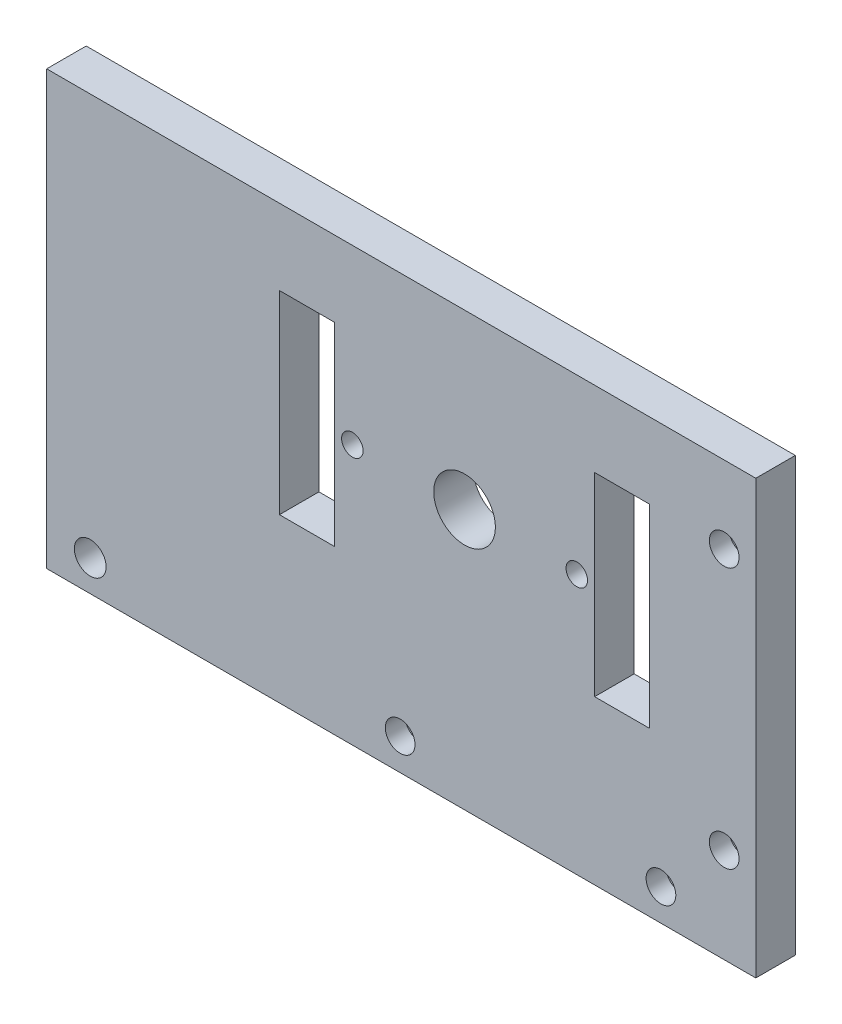
SolidWorks part; units mm, degrees
ref_plane "Front Plane" through (0, 0, 0) normal (0, 0, 1) x (1, 0, 0)
ref_plane "Top Plane" through (0, 0, 0) normal (0, 1, 0) x (1, 0, 0)
ref_plane "Right Plane" through (0, 0, 0) normal (1, 0, 0) x (0, 0, -1)
sketch "Brace Ref" plane through (0, 0, 0) normal (0, 0, 1) x (1, 0, 0)
  point P0 (0, 0)
  line B0 (-76.454, 5.6642) -> (-76.454, 10.0838)
  line B1 (-75.8588, 11.5206) -> (-73.7506, 13.6288)
  line B2 (-72.3138, 14.224) -> (-61.0148, 14.224)
  line B3 (-61.0148, 14.224) -> (-38.7641, 15.001)
  line B4 (-75.8588, 4.2274) -> (-73.7506, 2.1192)
  line B5 (-72.3138, 1.524) -> (-61.5696, 1.524)
  line B6 (-57.8366, 0) -> (-21.4114, 0)
  line B7 (-17.6784, 1.524) -> (-5.6642, 1.524)
  line B8 (-4.2274, 2.1192) -> (-2.1192, 4.2274)
  line B9 (-1.524, 5.6642) -> (-1.524, 17.6784)
  line B10 (0, 21.4114) -> (0, 57.8366)
  line B11 (-1.524, 61.5696) -> (-1.524, 72.3138)
  line B12 (-2.1192, 73.7506) -> (-4.2274, 75.8588)
  line B13 (-5.6642, 76.454) -> (-10.0838, 76.454)
  line B14 (-11.5206, 75.8588) -> (-13.6288, 73.7506)
  line B15 (-14.224, 72.3138) -> (-14.224, 61.0148)
  line B16 (-14.224, 61.0148) -> (-15.001, 38.7641)
  line B17 (-76.454, 0) -> (-76.454, 76.454) construction
  line B18 (-76.454, 0) -> (0, 0) construction
  line B19 (0, 0) -> (0, 76.454) construction
  line B20 (-76.454, 76.454) -> (0, 76.454) construction
  arc B21 (-76.454, 10.0838) -> (-75.8588, 11.5206) centre (-74.422, 10.0838) cw
  arc B22 (-73.7506, 13.6288) -> (-72.3138, 14.224) centre (-72.3138, 12.192) cw
  arc B23 (-38.7641, 15.001) -> (-27.0035, 18.4638) centre (-39.624, 39.624) ccw
  arc B24 (-27.0035, 18.4638) -> (-25.4333, 20.7849) centre (-28.6949, 21.2997) ccw
  arc B25 (-25.4333, 20.7849) -> (-20.7849, 25.4333) centre (-19.9136, 19.9136) cw
  arc B26 (-76.454, 5.6642) -> (-75.8588, 4.2274) centre (-74.422, 5.6642) ccw
  arc B27 (-73.7506, 2.1192) -> (-72.3138, 1.524) centre (-72.3138, 3.556) ccw
  arc B28 (-61.5696, 1.524) -> (-59.2587, 0.5806) centre (-61.5696, -1.778) cw
  arc B29 (-59.2587, 0.5806) -> (-57.8366, 0) centre (-57.8366, 2.032) ccw
  arc B30 (-21.4114, 0) -> (-19.9893, 0.5806) centre (-21.4114, 2.032) ccw
  arc B31 (-19.9893, 0.5806) -> (-17.6784, 1.524) centre (-17.6784, -1.778) cw
  arc B32 (-5.6642, 1.524) -> (-4.2274, 2.1192) centre (-5.6642, 3.556) ccw
  arc B33 (-2.1192, 4.2274) -> (-1.524, 5.6642) centre (-3.556, 5.6642) ccw
  arc B34 (-1.524, 17.6784) -> (-0.5806, 19.9893) centre (1.778, 17.6784) cw
  arc B35 (-0.5806, 19.9893) -> (0, 21.4114) centre (-2.032, 21.4114) ccw
  arc B36 (0, 57.8366) -> (-0.5806, 59.2587) centre (-2.032, 57.8366) ccw
  arc B37 (-0.5806, 59.2587) -> (-1.524, 61.5696) centre (1.778, 61.5696) cw
  arc B38 (-1.524, 72.3138) -> (-2.1192, 73.7506) centre (-3.556, 72.3138) ccw
  arc B39 (-4.2274, 75.8588) -> (-5.6642, 76.454) centre (-5.6642, 74.422) ccw
  arc B40 (-10.0838, 76.454) -> (-11.5206, 75.8588) centre (-10.0838, 74.422) ccw
  arc B41 (-13.6288, 73.7506) -> (-14.224, 72.3138) centre (-12.192, 72.3138) ccw
  arc B42 (-15.001, 38.7641) -> (-18.4638, 27.0035) centre (-39.624, 39.624) cw
  arc B43 (-18.4638, 27.0035) -> (-20.7849, 25.4333) centre (-21.2997, 28.6949) cw
  circle B44 centre (-70.104, 7.874) radius 4.3561
  circle B45 centre (-19.9136, 19.9136) radius 2.3813
  circle B46 centre (-7.874, 70.104) radius 4.3561
sketch_block_instance "Block1-1"
sketch_block "Block1" parameters "D1"=31.75, "D2"=30.48, "D3"=30.48, "D4"=31.75, "D5"=19.7104, "D6"=19.7104
sketch "Sketch5" plane through (0, 0, 0) normal (0, 0, 1) x (1, 0, 0)
  line L0 (-49.594, 49.547) -> (-49.594, 44.594) construction
  line L1 (-91.344, 72.344) -> (-2.794, 72.344)
  line L2 (-91.344, 72.344) -> (-91.344, 2.794)
  line L3 (-91.344, 2.794) -> (-2.794, 2.794)
  line L4 (-2.794, 72.344) -> (-2.794, 2.794)
  line L6 (-79.594, 60.594) -> (-19.594, 60.594) construction
  line L7 (-79.594, 60.594) -> (-79.594, 28.594) construction
  line L8 (-67.628, 44.594) -> (-49.594, 44.594) construction
  line L9 (-81.344, 62.344) -> (-17.844, 62.344) construction
  line L10 (-49.594, 44.594) -> (-31.56, 44.594) construction
  line L11 (-81.344, 62.344) -> (-81.344, 26.844) construction
  line L12 (-81.344, 26.844) -> (-17.844, 26.844) construction
  line L13 (-17.844, 62.344) -> (-17.844, 26.844) construction
  line L14 (-86.344, 67.344) -> (-12.844, 67.344) construction
  line L15 (-79.594, 28.594) -> (-19.594, 28.594) construction
  line L16 (-19.594, 60.594) -> (-19.594, 28.594) construction
  line L17 (-79.344, 60.194) -> (-70.494, 60.194)
  line L18 (-86.344, 67.344) -> (-86.344, 21.844) construction
  line L19 (-86.344, 21.844) -> (-12.844, 21.844) construction
  line L20 (-12.844, 67.344) -> (-12.844, 21.844) construction
  line L21 (-79.344, 60.194) -> (-79.344, 28.994)
  line L22 (-79.344, 28.994) -> (-70.494, 28.994)
  line L23 (-70.494, 60.194) -> (-70.494, 28.994)
  line L24 (-28.694, 60.194) -> (-19.844, 60.194)
  line L25 (-28.694, 60.194) -> (-28.694, 28.994)
  line L26 (-28.694, 28.994) -> (-19.844, 28.994)
  line L27 (-19.844, 60.194) -> (-19.844, 28.994)
  line L28 (-79.344, 60.194) -> (-79.594, 60.194) construction
  line L30 (-19.844, 60.194) -> (-19.594, 60.194) construction
  circle A7 centre (-49.594, 44.594) radius 4.953
  circle A10 centre (-19.9136, 19.9136) radius 3.683
  circle A14 centre (-59.944, 7.874) radius 1.5875
  circle A15 centre (-18.034, 7.874) radius 1.5875
  circle A16 centre (-7.874, 18.034) radius 1.5875
  circle A17 centre (-7.874, 59.944) radius 1.5875
  circle A18 centre (-19.9136, 19.9136) radius 2.3813 construction
  circle A19 centre (-67.628, 44.594) radius 1.6666 construction
  circle A21 centre (-31.56, 44.594) radius 1.6666 construction
  circle A22 centre (-39.594, 39.594) radius 0.5 construction
  circle A23 centre (-59.944, 7.874) radius 2.3876
  circle A24 centre (-18.034, 7.874) radius 2.3876
  circle A25 centre (-7.874, 59.944) radius 2.3876
  circle A26 centre (-7.874, 18.034) radius 2.3876
  circle A32 centre (-49.594, 44.594) radius 4.953
  circle A35 centre (-49.594, 44.594) radius 4.953
  circle A38 centre (-49.594, 44.594) radius 4.953
  point P6 (-49.594, 60.594)
  point P17 (-19.594, 44.594)
  point P25 (-49.594, 67.344)
  point P26 (-12.844, 44.594)
  point P39 (-70.494, 44.594)
  point P116 (-49.594, 44.594)
  dimension "D8" = 7.366
  dimension "D9" = 3.175
  dimension "D10" = 4.7752
  dimension "D2" = 9.906
  dimension "D22" = 3.3332
  dimension "D30" = 1
  dimension "D6" = 17.1196
  dimension "D7" = 17.1196
  dimension "D12" = 41.91
  dimension "D13" = 5.08
  dimension "D14" = 5.08
  dimension "D15" = 41.91
  dimension "D16" = 15.24
  dimension "D17" = 15.24
  dimension "D11" = 18.034
  dimension "D3" = 63.5
  dimension "D5" = 5
  dimension "D18" = 5
  dimension "D19" = 5
  dimension "D20" = 5
  dimension "D21" = 35.5
  dimension "D23" = 60
  dimension "D24" = 32
  dimension "D25" = 31.2
  dimension "D26" = 0.25
  dimension "D27" = 8.85
  dimension "D28" = 36.8
  dimension "D29" = 36.8
  dimension "D32" = 10
  dimension "D33" = 5
  dimension "D34" = 5
  dimension "D31" = 5
  dimension "D4" = 4
extrude "Boss-Extrude1" add sketch "Sketch5" along normal blind 6.35 contours L4 L1 L2 L3 A26 A25 A24 A23 A10 A7 L17 L23 L22 L21 L24 L27 L26 L25 | A25 A17 | A10 | A26 A16 | A24 A15 | A23 A14 region at (-47.302, 37.0786, 0) region at (-19.9136, 19.9136, 0) region at (-62.2641, 7.874, 0) region at (-20.3541, 7.874, 0) region at (-10.1941, 59.944, 0) region at (-10.1941, 18.034, 0)
hole_wizard "#8-32 Tapped Hole1" positions "3DSketch1" profile "Sketch6" tap size "#8-32" standard "ANSI Inch" end condition through all
sketch3d "3DSketch1"
  point P0 (-67.628, 44.594, 6.35)
  point P2 (-31.56, 44.594, 6.35)
  point P6 (-37.7438, 44.594, 6.35)
sketch "Sketch6" plane through (-67.628, 44.594, 6.35) normal (1, 0, 0) x (0, -1, 0)
  line L0 (0, 0) -> (0, 6.35)
  line L1 (0, 6.35) -> (1.7272, 6.35)
  line L2 (1.7272, 6.35) -> (1.7272, 0)
  line L5 (1.7272, 0) -> (0, 0)
  line L11 (0, -6.35) -> (0, 107.95) construction
  dimension "Thru Tap Drill Dia." = 3.4544
  dimension "Thru Tap Drill Depth" = 6.35
cosmetic thread "Hole Thread1" parameters "D2"=4.1656
cosmetic thread "Hole Thread2" parameters "D2"=4.1656
extrude "Cut-Extrude2" cut sketch "Sketch5<3>" against normal blind 3.175 from surface contours A24 A15 | A26 A16 | A23 A14 | A25 A17 region at (-62.2641, 7.874, 0) region at (-20.3541, 7.874, 0) region at (-10.1941, 59.944, 0) region at (-10.1941, 18.034, 0) starting at face at (-65.9008, 44.594, 6.35)
sketch "Sketch5<3>" plane through (0, 0, 0) normal (0, 0, 1) x (1, 0, 0) same geometry as "Sketch5"
fillet "Fillet1" [suppressed] radius 6.35
sketch "Sketch8" plane through (0, 0, 0) normal (0, 0, 1) x (1, 0, 0)
  line L1 (-91.344, 2.794) -> (-116.744, 2.794)
  line L2 (-91.344, 2.794) -> (-91.344, 72.344)
  line L3 (-91.344, 72.344) -> (-116.744, 72.344)
  line L4 (-116.744, 2.794) -> (-116.744, 72.344)
  circle A0 centre (-109.744, 7.794) radius 1
  point P5 (-107.8749, 7.0425)
  dimension "D2" = 2
  dimension "D1" = 25.4
  dimension "D3" = 5
  dimension "D4" = 7
extrude "Boss-Extrude2" add sketch "Sketch8" along normal up to surface (6.35 mm away) up to face at (-5.4864, 59.944, 6.35)
hole_wizard "1/4-20 Tapped Hole2" positions "3DSketch3" profile "Sketch10" tap size "1/4-20" standard "ANSI Inch" end condition through all
sketch3d "3DSketch3"
  line L0 (-109.744, 7.794, 6.35) -> (-109.744, 7.794, 0) construction
  point P0 (-109.744, 7.794, 6.35)
sketch "Sketch10" plane through (-109.744, 7.794, 6.35) normal (1, 0, 0) x (0, -1, 0)
  line L0 (0, 0) -> (0, 6.35)
  line L1 (0, 6.35) -> (2.5527, 6.35)
  line L2 (2.5527, 6.35) -> (2.5527, 0)
  line L5 (2.5527, 0) -> (0, 0)
  line L11 (0, -6.35) -> (0, 107.95) construction
  dimension "Thru Tap Drill Dia." = 5.1054
  dimension "Thru Tap Drill Depth" = 6.35
cosmetic thread "Hole Thread3" parameters "D2"=6.35
equation "\"D18@Sketch5\"=\"D5@Sketch5\""
equation "\"D19@Sketch5\"=\"D18@Sketch5\""
equation "\"D20@Sketch5\"=\"D5@Sketch5\""
equation "\"D29@Sketch5\"=\"D28@Sketch5\""
